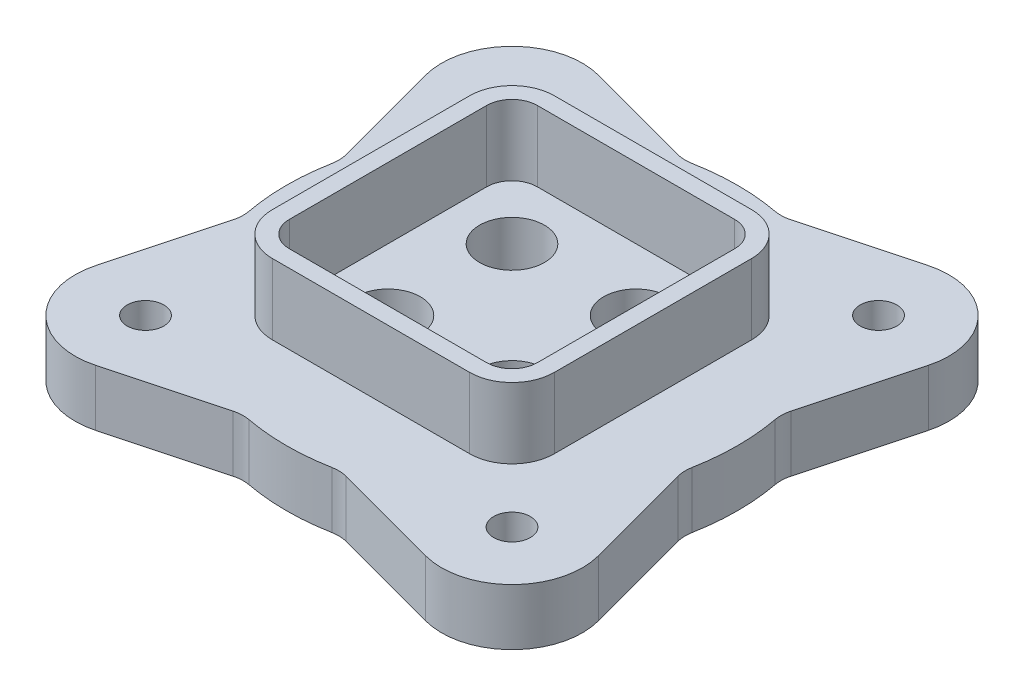
SolidWorks part; units mm, degrees
ref_plane "Front Plane" through (0, 0, 0) normal (0, 0, 1) x (1, 0, 0)
ref_plane "Top Plane" through (0, 0, 0) normal (0, 1, 0) x (1, 0, 0)
ref_plane "Right Plane" through (0, 0, 0) normal (1, 0, 0) x (0, 0, -1)
sketch "Sketch1" plane through (0, 0, 0) normal (0, 1, 0) x (1, 0, 0)
  line L0 (-1638.1239, 0) -> (1638.1239, 0) construction
  line L1 (-889, 1117.6) -> (889, 1117.6)
  line L2 (-889, -1270) -> (889, -1270)
  line L3 (-1270, -889) -> (-1270, 889)
  line L4 (-889, 1270) -> (889, 1270)
  line L5 (1270, -889) -> (1270, 889)
  line L6 (1117.6, -889) -> (1117.6, 889)
  line L7 (-889, -1117.6) -> (889, -1117.6)
  line L8 (-1117.6, -889) -> (-1117.6, 889)
  line L9 (0, 0) -> (0, 1117.6) construction
  line L10 (-850.9, 558.8) -> (-1117.6, 558.8) construction
  line L11 (-266.7, 558.8) -> (0, 558.8) construction
  line L12 (-1486.6499, 2264.3629) -> (-509.1298, 2002.4372)
  line L13 (-1651, 1651) -> (0, 0) construction
  line L14 (0, 1117.6) -> (0, 1754.7189) construction
  line L15 (-2264.3629, 1486.6499) -> (-2002.4372, 509.1298)
  line L16 (2264.3629, 1486.6499) -> (2002.4372, 509.1298)
  line L17 (1486.6499, 2264.3629) -> (509.1298, 2002.4372)
  line L18 (2264.3629, -1486.6499) -> (2002.4372, -509.1298)
  line L19 (1486.6499, -2264.3629) -> (509.1298, -2002.4372)
  line L20 (-1486.6499, -2264.3629) -> (-509.1298, -2002.4372)
  line L21 (-2264.3629, -1486.6499) -> (-2002.4372, -509.1298)
  arc A0 (1270, 889) -> (889, 1270) centre (889, 889) ccw
  arc A1 (-889, 1270) -> (-1270, 889) centre (-889, 889) ccw
  arc A2 (1270, -889) -> (889, -1270) centre (889, -889) cw
  arc A3 (-889, -1270) -> (-1270, -889) centre (-889, -889) cw
  arc A4 (1117.6, 889) -> (889, 1117.6) centre (889, 889) ccw
  arc A5 (1117.6, -889) -> (889, -1117.6) centre (889, -889) cw
  arc A6 (-889, -1117.6) -> (-1117.6, -889) centre (-889, -889) cw
  arc A7 (-889, 1117.6) -> (-1117.6, 889) centre (-889, 889) ccw
  circle A8 centre (-558.8, 558.8) radius 292.1
  circle A9 centre (558.8, 558.8) radius 292.1
  circle A10 centre (-1651, 1651) radius 165.1
  arc A11 (-1486.6499, 2264.3629) -> (-2264.3629, 1486.6499) centre (-1651, 1651) ccw
  arc A12 (374.1233, 1997.2621) -> (-374.1233, 1997.2621) centre (0, 0) ccw
  arc A13 (-509.1298, 2002.4372) -> (-374.1233, 1997.2621) centre (-430.2418, 2296.8514) ccw
  arc A14 (-1997.2621, -374.1233) -> (-1997.2621, 374.1233) centre (0, 0) cw
  arc A15 (-2002.4372, 509.1298) -> (-1997.2621, 374.1233) centre (-2296.8514, 430.2418) cw
  circle A16 centre (1651, 1651) radius 165.1
  arc A17 (1997.2621, -374.1233) -> (1997.2621, 374.1233) centre (0, 0) ccw
  arc A18 (2002.4372, 509.1298) -> (1997.2621, 374.1233) centre (2296.8514, 430.2418) ccw
  arc A19 (1486.6499, 2264.3629) -> (2264.3629, 1486.6499) centre (1651, 1651) cw
  arc A20 (509.1298, 2002.4372) -> (374.1233, 1997.2621) centre (430.2418, 2296.8514) cw
  circle A21 centre (-1651, -1651) radius 165.1
  arc A22 (2002.4372, -509.1298) -> (1997.2621, -374.1233) centre (2296.8514, -430.2418) cw
  arc A23 (509.1298, -2002.4372) -> (374.1233, -1997.2621) centre (430.2418, -2296.8514) ccw
  arc A24 (1486.6499, -2264.3629) -> (2264.3629, -1486.6499) centre (1651, -1651) ccw
  circle A25 centre (1651, -1651) radius 165.1
  arc A26 (-509.1298, -2002.4372) -> (-374.1233, -1997.2621) centre (-430.2418, -2296.8514) cw
  arc A27 (374.1233, -1997.2621) -> (-374.1233, -1997.2621) centre (0, 0) cw
  arc A28 (-2002.4372, -509.1298) -> (-1997.2621, -374.1233) centre (-2296.8514, -430.2418) ccw
  arc A29 (-1486.6499, -2264.3629) -> (-2264.3629, -1486.6499) centre (-1651, -1651) cw
  circle A30 centre (558.8, -558.8) radius 292.1
  circle A31 centre (-558.8, -558.8) radius 292.1
  point P1 (0, 0)
  point P4 (0, 0)
  point P46 (0, 0)
  point P63 (0, 2032)
  point P80 (0, -2032)
  dimension "D1" = 381
  dimension "D2" = 381
  dimension "D4" = 558.8
  dimension "D6" = 584.2
  dimension "D7" = 1651
  dimension "D8" = 330.2
  dimension "D9" = 60
  dimension "D10" = 304.8
  dimension "D12" = 635
  dimension "D13" = 2032
  dimension "D5" = 2540
  dimension "D11" = 75
  dimension "D3" = 152.4
extrude "Boss-Extrude1" add sketch "Sketch1" along normal blind 508 contours A29 L20 A26 A27 A23 L19 A24 L18 A22 A17 A18 L16 A19 L17 A20 A12 A13 L12 A11 L15 A15 A14 A28 L21 A25 A16 A10 L2 A3 L3 A1 L4 A0 L5 A2 A21 | A3 L2 A2 L5 A0 L4 A1 L3 A7 L1 A4 L6 A5 L7 A6 L8 | L1 A7 L8 A6 L7 A5 L6 A4 A9 A8 A30 A31 region at (0, 0, 0) region at (-1133.0077, 0, 1133.0077) region at (-1014.6245, 0, -2070.9454)
extrude "Boss-Extrude2" add sketch "Sketch1<3>" along normal blind 635 from offset 508 contours A3 L2 A2 L5 A0 L4 A1 L3 A7 L1 A4 L6 A5 L7 A6 L8 region at (-1133.0077, 0, 1133.0077)
sketch "Sketch1<3>" plane through (0, 0, 0) normal (0, 1, 0) x (1, 0, 0) same geometry as "Sketch1"
sketch "Sketch2" plane through (0, 0, 0) normal (0, -1, 0) x (1, 0, 0)
  circle A0 centre (0, 0) radius 1333.5
  circle A1 centre (0, 0) radius 1841.5
  dimension "D1" = 2667
  dimension "D2" = 3683
extrude "Cut-Extrude1" cut sketch "Sketch2" against normal blind 76.2
